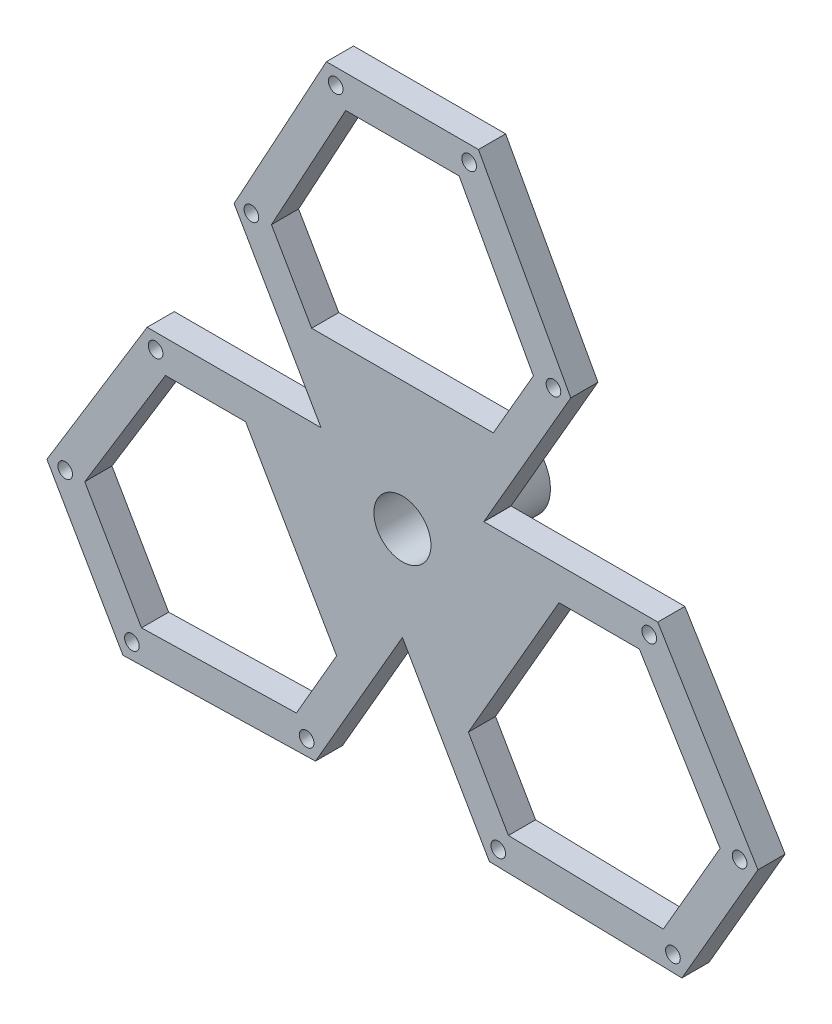
SolidWorks part; units mm, degrees
ref_plane "Front Plane" through (0, 0, 0) normal (0, 0, 1) x (1, 0, 0)
ref_plane "Top Plane" through (0, 0, 0) normal (0, 1, 0) x (1, 0, 0)
ref_plane "Right Plane" through (0, 0, 0) normal (1, 0, 0) x (0, 0, -1)
sketch "Sketch1" plane through (0, 0, 0) normal (0, 0, 1) x (1, 0, 0)
  line L0 (0, 17.3205) -> (0, 67.5) construction
  line L1 (15, 8.6603) -> (10, 17.3205) construction
  line L2 (0, 17.3205) -> (-10, 17.3205) construction
  line L3 (-15, 8.6603) -> (-20, 0) construction
  line L4 (-20, 0) -> (-15, -8.6603) construction
  line L5 (-10, -17.3205) -> (0, -17.3205) construction
  line L6 (15, -8.6603) -> (20, 0) construction
  line L7 (77.9423, 0) -> (38.9711, 67.5) construction
  line L8 (38.9711, 67.5) -> (-38.9711, 67.5) construction
  line L9 (-38.9711, 67.5) -> (-77.9423, 0) construction
  line L10 (-77.9423, 0) -> (-38.9711, -67.5) construction
  line L11 (-38.9711, -67.5) -> (38.9711, -67.5) construction
  line L12 (38.9711, -67.5) -> (77.9423, 0) construction
  line L14 (-30.995, 36.3817) -> (-14, 67.5)
  line L18 (10, 17.3205) -> (0, 17.3205) construction
  line L19 (-15, -8.6603) -> (-10, -17.3205) construction
  line L20 (10, -17.3205) -> (15, -8.6603) construction
  line L21 (-10, 17.3205) -> (-15, 8.6603) construction
  line L22 (20, 0) -> (15, 8.6603) construction
  line L23 (0, -17.3205) -> (10, -17.3205) construction
  line L24 (-10, 17.3205) -> (-14.995, 8.6689) construction
  line L25 (-15, 8.6603) -> (-14.995, 8.6689)
  line L26 (-14.995, 8.6689) -> (-30.995, 36.3817)
  line L27 (14, 67.5) -> (-14, 67.5)
  line L28 (30.995, 36.3817) -> (14, 67.5)
  line L29 (14.995, 8.6689) -> (30.995, 36.3817)
  line L30 (15, 8.6603) -> (14.995, 8.6689)
  line L31 (15, 8.6603) -> (15.005, 8.6516)
  line L32 (15.005, 8.6516) -> (47.005, 8.6516)
  line L33 (47.005, 8.6516) -> (65.4567, -21.6256)
  line L34 (51.4567, -45.8744) -> (65.4567, -21.6256)
  line L35 (16.01, -45.0333) -> (51.4567, -45.8744)
  line L36 (0.01, -17.3205) -> (16.01, -45.0333)
  line L37 (0, -17.3205) -> (0.01, -17.3205)
  line L38 (0, -17.3205) -> (-0.01, -17.3205)
  line L39 (-0.01, -17.3205) -> (-16.01, -45.0333)
  line L40 (-16.01, -45.0333) -> (-51.4567, -45.8744)
  line L41 (-65.4567, -21.6256) -> (-51.4567, -45.8744)
  line L42 (-47.005, 8.6516) -> (-65.4567, -21.6256)
  line L43 (-15.005, 8.6516) -> (-47.005, 8.6516)
  line L44 (-15, 8.6603) -> (-15.005, 8.6516)
  arc A0 (15, 8.6603) -> (0, 17.3205) centre (0, 0) ccw construction
  circle A1 centre (0, 0) radius 67.5 construction
  arc A2 (15, -8.6603) -> (15, 8.6603) centre (0, 0) ccw construction
  arc A3 (0, -17.3205) -> (15, -8.6603) centre (0, 0) ccw construction
  arc A4 (0, 17.3205) -> (-15, 8.6603) centre (0, 0) ccw construction
  arc A5 (-15, -8.6603) -> (0, -17.3205) centre (0, 0) ccw construction
  arc A6 (-15, 8.6603) -> (-15, -8.6603) centre (0, 0) ccw construction
  point P47 (0, 0)
  dimension "D1" = 20
  dimension "D2" = 135
  dimension "D3" = 14
  dimension "D4" = 9.99
  dimension "D5" = 32
  dimension "D6" = 120
  dimension "D7" = 3
extrude "Boss-Extrude1" add sketch "Sketch1" along normal blind 5
sketch "Sketch2" plane through (0, 0, 5) normal (0, 0, 1) x (1, 0, 0)
  line L0 (-15.005, 8.6516) -> (0.01, -17.3205) construction
  line L1 (-20.4956, -11.8211) -> (-7.4975, -4.3345) construction
  line L2 (-15.005, 8.6516) -> (15.005, 8.6516) construction
  line L3 (15.005, 8.6516) -> (0.01, -17.3205) construction
  line L5 (-28.8721, 2.6516) -> (-12.119, -26.2939)
  line L20 (-19.5212, -39.1149) -> (-5.2062, -14.3205)
  line L21 (-48.0404, -39.7916) -> (-19.5212, -39.1149)
  line L22 (-58.4807, -21.7084) -> (-48.0404, -39.7916)
  line L23 (-43.6351, 2.6516) -> (-58.4807, -21.7084)
  line L24 (-15.005, 2.6516) -> (-43.6351, 2.6516)
  line L25 (-19.5212, -39.1149) -> (-12.119, -26.2939)
  line L26 (-48.0404, -39.7916) -> (-19.5212, -39.1149)
  line L27 (-58.4807, -21.7084) -> (-48.0404, -39.7916)
  line L28 (-43.6351, 2.6516) -> (-58.4807, -21.7084)
  line L29 (-28.8721, 2.6516) -> (-43.6351, 2.6516)
  line L31 (-24.1139, 36.4633) -> (-16.7117, 23.6423)
  line L32 (16.7324, 23.6782) -> (-16.7117, 23.6423)
  line L33 (16.7324, 23.6782) -> (24.1139, 36.4633)
  line L34 (24.1139, 36.4633) -> (10.4404, 61.5)
  line L35 (10.4404, 61.5) -> (-10.4404, 61.5)
  line L36 (-10.4404, 61.5) -> (-24.1139, 36.4633)
  line L37 (43.6351, 2.6516) -> (28.8306, 2.6516)
  line L38 (12.1397, -26.3298) -> (28.8306, 2.6516)
  line L39 (12.1397, -26.3298) -> (19.5212, -39.1149)
  line L40 (19.5212, -39.1149) -> (48.0404, -39.7916)
  line L41 (48.0404, -39.7916) -> (58.4807, -21.7084)
  line L42 (58.4807, -21.7084) -> (43.6351, 2.6516)
  point P31 (0, -1.1576)
  point P32 (0, 0)
  dimension "D2" = 15
  dimension "D1" = 6
  dimension "D3" = 3
extrude "Cut-Extrude1" cut sketch "Sketch2" against normal through all
sketch "Sketch5" plane through (0, 0, 5) normal (0, 0, 1) x (1, 0, 0)
  line L0 (-47.005, 8.6516) -> (-43.8811, 3.0895) construction
  line L1 (-65.4567, -21.6256) -> (-58.7141, -21.7056) construction
  line L2 (-51.4567, -45.8744) -> (-48.1547, -39.9951) construction
  line L3 (-16.01, -45.0333) -> (-19.265, -39.5469) construction
  line L4 (30.995, 36.3817) -> (24.6161, 36.4574) construction
  line L5 (14, 67.5) -> (10.5594, 61.7007) construction
  line L6 (-14, 67.5) -> (-10.5594, 61.7007) construction
  line L7 (-30.995, 36.3817) -> (-24.6161, 36.4574) construction
  line L8 (16.01, -45.0333) -> (19.265, -39.5469) construction
  line L9 (51.4567, -45.8744) -> (48.1547, -39.9951) construction
  line L10 (65.4567, -21.6256) -> (58.7141, -21.7056) construction
  line L11 (47.005, 8.6516) -> (43.8811, 3.0895) construction
  circle A0 centre (-45.443, 5.8705) radius 1.35
  circle A1 centre (-62.0854, -21.6656) radius 1.35
  circle A2 centre (-49.8057, -42.9347) radius 1.35
  circle A3 centre (-17.6375, -42.2901) radius 1.35
  circle A4 centre (27.8056, 36.4196) radius 1.35
  circle A5 centre (12.2797, 64.6003) radius 1.35
  circle A6 centre (-12.2797, 64.6003) radius 1.35
  circle A7 centre (-27.8056, 36.4196) radius 1.35
  circle A8 centre (17.6375, -42.2901) radius 1.35
  circle A9 centre (49.8057, -42.9347) radius 1.35
  circle A10 centre (62.0854, -21.6656) radius 1.35
  circle A11 centre (45.443, 5.8705) radius 1.35
  point P48 (0, 0)
  point P49 (0, 0)
  dimension "D1" = 2.7
sketch "Sketch6" plane through (0, 0, 0) normal (0, 0, -1) x (-1, 0, 0)
  circle A0 centre (0, 0) radius 7.25
  dimension "D1" = 14.5
extrude "Boss-Extrude3" add sketch "Sketch6" along normal blind 15 contours A0
sketch "Sketch3" plane through (0, 0, -15) normal (0, 0, -1) x (-1, 0, 0)
  circle A0 centre (0, 0) radius 5.25
  dimension "D1" = 10.5
extrude "Cut-Extrude2" cut sketch "Sketch3" against normal up to surface (20 mm away) up to face at (35.108, -20.2736, 5)
extrude "Cut-Extrude3" cut sketch "Sketch5" against normal up to surface (5 mm away) up to face at (7.25, 0, 0)
